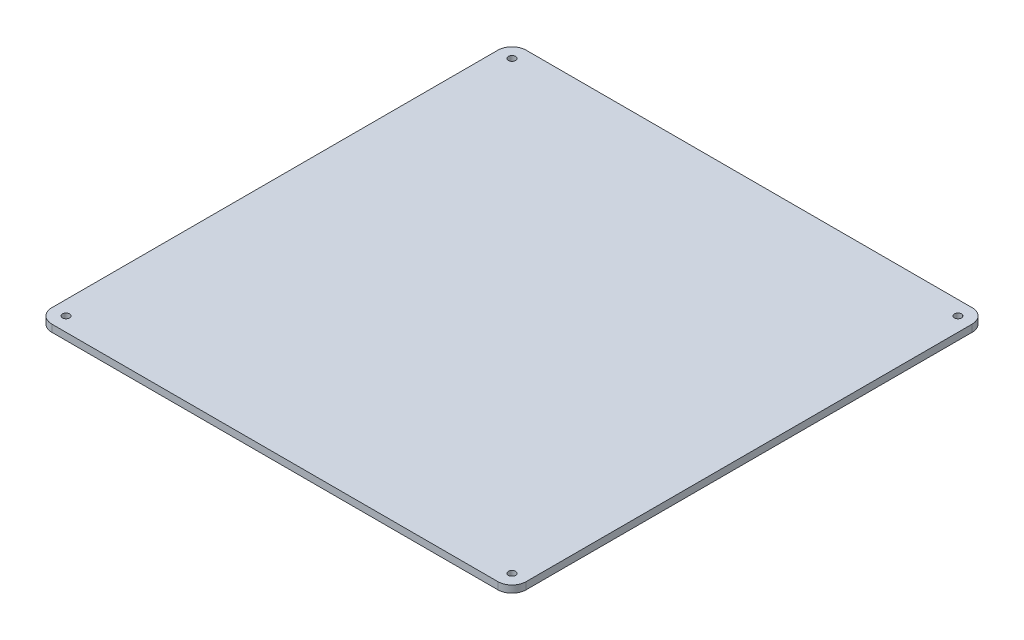
SolidWorks part; units mm, degrees
ref_plane "Front Plane" through (0, 0, 0) normal (0, 0, 1) x (1, 0, 0)
ref_plane "Top Plane" through (0, 0, 0) normal (0, 1, 0) x (1, 0, 0)
ref_plane "Right Plane" through (0, 0, 0) normal (1, 0, 0) x (0, 0, -1)
sketch "Sketch1" plane through (0, 0, 0) normal (0, 1, 0) x (1, 0, 0)
  line L1 (0, 0) -> (200, 0)
  line L2 (0, 0) -> (0, 200)
  line L3 (0, 200) -> (200, 200)
  line L4 (200, 0) -> (200, 200)
extrude "Boss-Extrude1" add sketch "Sketch1" along normal blind 3
fillet "Fillet1" radius 6 1 edges at (0, 1.5, -200) type face fillet first side face at (0, 1.5, -100) second side face at (100, 1.5, -200)
fillet "Fillet2" radius 6 1 edges at (200, 1.5, -200) type face fillet first side face at (200, 1.5, -100) second side face at (103, 1.5, -200)
fillet "Fillet3" radius 6 1 edges at (200, 1.5, 0) type face fillet first side face at (200, 1.5, -97) second side face at (100, 1.5, 0)
fillet "Fillet4" radius 6 1 edges at (0, 1.5, 0) type face fillet first side face at (0, 1.5, -97) second side face at (97, 1.5, 0)
sketch "Sketch2" plane through (0, 3, 0) normal (0, 1, 0) x (1, 0, 0)
  line L0 (100, 200) -> (100, -37.3926) construction
  line L1 (194, 200) -> (6, 200) construction
  line L2 (0, 100) -> (254.8165, 100) construction
  line L3 (0, 194) -> (0, 6) construction
  circle A0 centre (6, 194) radius 1.5
  circle A1 centre (194, 194) radius 1.5
  circle A2 centre (6, 6) radius 1.5
  circle A3 centre (194, 6) radius 1.5
  dimension "D1" = 6
  dimension "D2" = 6
extrude "Cut-Extrude1" cut sketch "Sketch2" against normal through all
